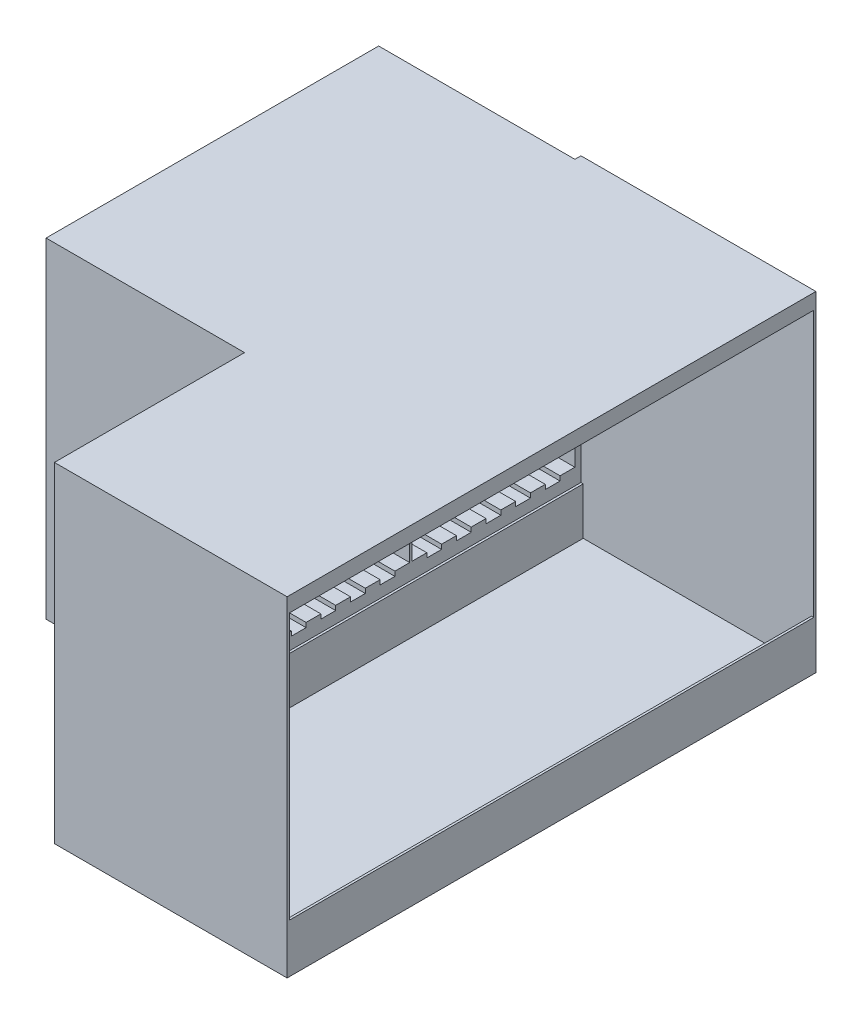
SolidWorks part; units mm, degrees
other "Исправление1"
sketch "Эскиз13" plane through (1050, -360, 1224.5) normal (0.916, -0.3443, 0.206) x (0.3981, 0.8438, -0.36)
ref_plane "Спереди" through (0, 0, 0) normal (0, 0, 1) x (1, 0, 0)
ref_plane "Сверху" through (0, 0, 0) normal (0, 1, 0) x (1, 0, 0)
ref_plane "Справа" through (0, 0, 0) normal (1, 0, 0) x (0, 0, -1)
other "Configuration Table"
sketch "Основа эскиз" plane through (0, 0, 0) normal (1, 0, 0) x (0, 0, -1)
  line L1 (-447, 435.8) -> (447, 435.8)
  line L2 (-447, 435.8) -> (-447, -435.8)
  line L3 (-447, -435.8) -> (447, -435.8)
  line L4 (447, 435.8) -> (447, -435.8)
  point P4 (0, 435.8)
  point P8 (-447, 0)
  dimension "D2" = 894
  dimension "D1" = 871.6
extrude "Основа" add sketch "Основа эскиз" along normal blind 1138.3
sketch "Вырез коретки эскиз" plane through (1138.3, 0, 0) normal (1, 0, 0) x (0, 0, -1)
  line L5 (447, 435.8) -> (-447, 435.8) construction
  line L6 (-447, 395.8) -> (441, 395.8)
  line L7 (-447, -435.8) -> (447, -435.8) construction
  line L8 (-447, 395.8) -> (-447, -305.2)
  line L9 (-447, -305.2) -> (441, -305.2)
  line L10 (441, 395.8) -> (441, -305.2)
  line L11 (-447, 435.8) -> (-447, -435.8) construction
  line L12 (447, -435.8) -> (447, 435.8) construction
  point P0 (0, 0)
  dimension "D1" = 40
  dimension "D3" = 6
  dimension "D4" = 130.6
extrude "Вырез коретки" cut sketch "Вырез коретки эскиз" against normal blind 614.3
sketch "вырез ячейки эскиз" plane through (524, 0, 0) normal (1, 0, 0) x (0, 0, -1)
  line L0 (441, 395.8) -> (-447, 395.8) construction
  line L1 (-441, 395.8) -> (-11, 395.8)
  line L2 (-441, 395.8) -> (-441, 75.8)
  line L3 (-441, 75.8) -> (-11, 75.8)
  line L4 (-11, 395.8) -> (-11, 75.8)
  line L17 (-447, 395.8) -> (-447, -305.2) construction
  dimension "D7" = 430
  dimension "D8" = 320
  dimension "D1" = 6
extrude "вырез ячейки" cut sketch "вырез ячейки эскиз" against normal blind 506
sketch "вырез двери эскиз" plane through (0, 0, 0) normal (-1, 0, 0) x (0, 0, 1)
  line L1 (11, 395.8) -> (441, 395.8)
  line L2 (11, 395.8) -> (11, 75.8)
  line L3 (11, 75.8) -> (441, 75.8)
  line L4 (441, 395.8) -> (441, 75.8)
  line L6 (441, 75.8) -> (11, 75.8) construction
  line L7 (11, 75.8) -> (11, 395.8) construction
  line L8 (441, 395.8) -> (441, 75.8) construction
  line L9 (441, 395.8) -> (441, 75.8) construction
  line L10 (11, 395.8) -> (441, 395.8) construction
extrude "вырез двери" cut sketch "вырез двери эскиз" against normal through all
sketch "Вырез основание низ эскиз" plane through (0, -305.2, 0) normal (0, 1, 0) x (1, 0, 0)
  line L0 (1138.3, -447) -> (1138.3, 441) construction
  line L1 (530, 441) -> (1132.3, 441)
  line L2 (530, 441) -> (530, -447)
  line L3 (530, -447) -> (1132.3, -447)
  line L4 (1132.3, 441) -> (1132.3, -447)
  line L5 (524, 441) -> (1138.3, 441) construction
  line L6 (524, -447) -> (1138.3, -447) construction
  dimension "D1" = 6
  dimension "D2" = 602.3
extrude "Вырез основание низ" cut sketch "Вырез основание низ эскиз" against normal blind 124.6
sketch "Вырез основания верх эскиз" plane through (0, 395.8, 0) normal (0, -1, 0) x (1, 0, 0)
  line L0 (524, 447) -> (1138.3, 447) construction
  line L1 (530, -441) -> (1132.3, -441)
  line L2 (530, -441) -> (530, 447)
  line L3 (530, 447) -> (1132.3, 447)
  line L4 (1132.3, -441) -> (1132.3, 447)
  line L5 (524, -441) -> (1138.3, -441) construction
  line L6 (1138.3, -441) -> (1138.3, 447) construction
  dimension "D1" = 6
  dimension "D2" = 602.3
extrude "Вырез основание верх" cut sketch "Вырез основания верх эскиз" against normal offset from surface (34 mm away) 6 up to face at (569.15, 435.8, 0)
sketch "вырез полозья эскиз" plane through (524, 0, 0) normal (1, 0, 0) x (0, 0, -1)
  line L0 (-441, 75.8) -> (-11, 75.8) construction
  line L1 (-401.9091, 75.8) -> (-362.8182, 75.8)
  line L2 (-401.9091, 75.8) -> (-401.9091, 63.8)
  line L3 (-401.9091, 63.8) -> (-362.8182, 63.8)
  line L4 (-362.8182, 75.8) -> (-362.8182, 63.8)
  dimension "D2" = 39.0909
  dimension "D3" = 39.0909
extrude "Вырез полозья" cut sketch "вырез полозья эскиз" against normal blind 506
pattern_linear "Линейный массив полозьев" count 5 spacing 78.1818 along (0, 0, -1) of "Вырез полозья"
pattern_linear "Линейный массив ячеек" count 2 spacing 436 along (0, 0, -1) count 2 spacing 338 along (0, -1, 0) of "Линейный массив полозьев", "вырез двери", "вырез ячейки"
sketch "Основание эскиз" plane through (0, 0, 447) normal (0, 0, 1) x (1, 0, 0)
  line L0 (1138.3, -435.8) -> (1138.3, -305.2)
  line L1 (1138.3, -305.2) -> (1132.3, -305.2)
  line L2 (1132.3, -305.2) -> (1132.3, -429.8)
  line L3 (1132.3, -429.8) -> (530, -429.8)
  line L4 (530, -429.8) -> (530, -305.2)
  line L5 (530, -305.2) -> (524, -305.2)
  line L6 (524, -305.2) -> (524, -435.8)
  line L7 (1138.3, -435.8) -> (0, -435.8) construction
  line L8 (524, -435.8) -> (1138.3, -435.8)
  line L9 (1132.3, 395.8) -> (1138.3, 395.8)
  line L10 (1138.3, 395.8) -> (1138.3, 435.8)
  line L11 (1138.3, 435.8) -> (524, 435.8)
  line L12 (1138.3, 435.8) -> (0, 435.8) construction
  line L13 (524, 435.8) -> (524, 395.8)
  line L14 (524, 395.8) -> (530, 395.8)
  line L15 (530, 395.8) -> (530, 429.8)
  line L16 (530, 429.8) -> (1132.3, 429.8)
  line L17 (1132.3, 429.8) -> (1132.3, 395.8)
extrude "Основание" add sketch "Основание эскиз" along normal blind 496
sketch "Стенка боквая эскиз" plane through (0, 0, 943) normal (0, 0, 1) x (1, 0, 0)
  line L1 (1138.3, 435.8) -> (524, 435.8)
  line L2 (1138.3, 435.8) -> (1138.3, -435.8)
  line L3 (1138.3, -435.8) -> (524, -435.8)
  line L4 (524, 435.8) -> (524, -435.8)
extrude "Стенка боковая" add sketch "Стенка боквая эскиз" along normal blind 6
sketch "Эскиз14" plane through (0, 0, -447) normal (0, 0, -1) x (-1, 0, 0)
  line L0 (-1138.3, 435.8) -> (0, 435.8) construction
  line L1 (0, -435.8) -> (-518, -435.8)
  line L2 (0, -435.8) -> (0, 435.8)
  line L3 (0, 435.8) -> (-518, 435.8)
  line L4 (-518, -435.8) -> (-518, 435.8)
  line L6 (-524, -305.2) -> (-524, 395.8) construction
  dimension "D1" = 6
extrude "Вырез-Вытянуть1" cut sketch "Эскиз14" against normal offset from surface (16 mm away) 6
sketch "Эскиз15" plane through (1138.3, 0, 0) normal (1, 0, 0) x (0, 0, -1)
  line L1 (-943, -305.2) -> (441, -305.2)
  line L2 (-943, -305.2) -> (-943, -429.8)
  line L3 (-943, -429.8) -> (441, -429.8)
  line L4 (441, -305.2) -> (441, -429.8)
extrude "Вырез-Вытянуть2" cut sketch "Эскиз15" against normal up to next
sketch "Эскиз16" plane through (1138.3, 0, 0) normal (1, 0, 0) x (0, 0, -1)
  line L0 (441, -306.58) -> (441, -429.8)
  line L2 (-943, -429.8) -> (441, -429.8)
  line L3 (-943, -429.8) -> (-943, -306.58)
  line L4 (-943, -306.58) -> (441, -306.58)
  line L7 (441, -429.8) -> (441, 395.8) construction
  dimension "D1" = 123.22
extrude "Бобышка-Вытянуть1" add sketch "Эскиз16" against normal blind 6
equation "\"Ширина груза\"= 420"
equation "\"Глубина груза\"= 490"
equation "\"Высота груза\"= 297"
equation "\"Ширина ячейки\"= \"Ширина груза\" + 10"
equation "\"Глубина ячейки\"= \"Глубина груза\" + 10"
equation "\"Высота ячейки\"= \"Высота груза\" + 10 + 13"
equation "\"Колво ячеек ширина\"= 2"
equation "\"Колво ячеек высота\"= 2"
equation "\"Толщина стенки\" = 6"
equation "\"D2@Основа эскиз\"=( \"Ширина ячейки\" + \"Толщина стенки\" + \"Крепление дверцы\" ) * \"Колво ячеек ширина\" + \"Толщина стенки\"*2"
equation "\"D1@Основа эскиз\"=( \"Высота ячейки\" + \"Толщина стенки\" + \"Высота пола\" ) * \"Колво ячеек высота\" + \"Толщина стенки\" * 6 + \"Мотор X ширина корпуса\" + \"Мотор Y ширина корпуса\"+40+20+15"
equation "\"Крепление дверцы\"= 5 "
equation "\"D7@вырез ячейки эскиз\"= \"Ширина ячейки\""
equation "\"D1@вырез ячейки эскиз\"=\"Толщина стенки\" "
equation "\"D8@вырез ячейки эскиз\"= \"Высота ячейки\""
equation "\"D1@Основа\"=\"Глубина ячейки\" + \"Глубина каретки\" + \"Толщина стенки\" * 6 + \"Ширина рейки\""
equation "\"D1@Вырез коретки\"=\"Глубина каретки\" + \"Толщина стенки\" * 2 + \"Ширина рейки\""
equation "\"D1@Вырез основание низ эскиз\"=\"Толщина стенки\" "
equation "\"Ширина рейки\"= \"Толщина шестерни\""
equation "\"D1@вырез ячейки\"= \"Глубина ячейки\" + \"Толщина стенки\""
equation "\"D1\"= \"Толщина стенки\""
equation "\"D2@Вырез основание низ эскиз\"=\"Глубина каретки\" + \"Ширина рейки\""
equation "\"Высота рейки\"= 20"
equation "\"D1@Вырез основания верх эскиз\"=\"Толщина стенки\""
equation "\"D2@Вырез основания верх эскиз\"=\"Глубина каретки\" + \"Ширина рейки\" "
equation "\"D1@Вырез основание верх\"=\"Толщина стенки\""
equation "\"D4@Вырез коретки эскиз\"=\"Толщина стенки\"  + \"Высота рейки\" + \"Отступ рейки\" + \"Мотор X ширина корпуса\" + \"Мотор Y ширина корпуса\""
equation "\"D1@Вырез коретки эскиз\"=\"Толщина стенки\"*2+28"
equation "\"D3@Вырез коретки эскиз\" = \"Толщина стенки\""
equation "\"D1@Вырез основание низ\"=\"Мотор X ширина корпуса\" + \"Мотор Y ширина корпуса\"+\"Высота рейки\" + \"Отступ рейки\""
equation "\"Высота пола\"= \"Толщина стенки\" * 2"
equation "\"Колво полозьев\"= 5"
equation "\"D1@вырез полозья эскиз\" = \"Высота пола\""
equation "\"D2@вырез полозья эскиз\" = \"Ширина ячейки\" /  ( \"Колво полозьев\" * 2 + 1 ) "
equation "\"D3@вырез полозья эскиз\"= \"Ширина ячейки\" / ( \"Колво полозьев\" * 2 + 1 )"
equation "\"D1@Вырез полозья\" = \"Глубина ячейки\" + \"Толщина стенки\""
equation "\"D1@Линейный массив полозьев\" = \"Колво полозьев\""
equation "\"D3@Линейный массив полозьев\" = \"Ширина ячейки\" /  ( \"Колво полозьев\" * 2 + 1 )  * 2"
equation "\"D1@Линейный массив ячеек\" = \"Колво ячеек ширина\""
equation "\"D2@Линейный массив ячеек\" = \"Колво ячеек высота\""
equation "\"D3@Линейный массив ячеек\" = \"Ширина ячейки\" + \"Толщина стенки\""
equation "\"D4@Линейный массив ячеек\" = \"Высота ячейки\" + \"Высота пола\" + \"Толщина стенки\""
equation "\"Отступ рейки\"= 20"
equation "\"Глубина каретки\"= \"Глубина ячейки\" + 30 + \"Мотор Y высота корпуса\" + 20"
equation "\"D1@Стенка боковая\" = \"Толщина стенки\""
equation "\"Длинна рейки\"= ( \"Ширина ячейки\" + \"Толщина стенки\" + \"Крепление дверцы\" ) * \"Колво ячеек ширина\" + \"Ширина ячейки выгрузки\" * \"Колво выгрузки\" + \"Толщина стенки\""
equation "\"D1@Основание\" = \"Длинна рейки\" -  ( \"Ширина ячейки\" + \"Толщина стенки\" + \"Крепление дверцы\" )  * \"Колво ячеек ширина\" - \"Толщина стенки\""
equation "\"Отступ шпильки\"= 26"
equation "\"Диаметр шпильки\"= 5"
equation "\"Длинна шпильки\"= ( \"Высота ячейки\" + \"Толщина стенки\" + \"Высота пола\" ) * \"Колво ячеек высота\" + ( \"Толщина стенки\" + \"Отступ рейки\" ) * 2 "
equation "\"Ширина пластины\"= 50  "
equation "\"Высота зона выгрузки\"= \"Высота ячейки\" * 2 + \"Толщина стенки\" * 2"
equation "\"Колво выгрузки\"= 1"
equation "\"D1@Вырез-Вытянуть1\"=\"Толщина стенки\""
equation "\"Ширина ячейки выгрузки\"= \"Ширина ячейки\" + \"Толщина стенки\" + \"Отступ крепления мотора фиксации\"*2"
equation "\"Отступ крепления мотора фиксации\" = 30"
equation "\"Мотор X ширина корпуса\"= 42.3"
equation "\"Мотор X высота корпуса\"= 42.3"
equation "\"Мотор X длина корпуса\"= 40"
equation "\"Мотор X вылет вала\"= 19.8"
equation "\"Мотор Y ширина корпуса\"= 42.3"
equation "\"Мотор Y высота корпуса\"= 42.3"
equation "\"Мотор Y длина корпуса\"= 48"
equation "\"Мотор Y вылет вала\"= 30"
equation "\"Мотор Z ширина корпуса\"= 42"
equation "\"Мотор Z высота корпуса\"= 42"
equation "\"Мотор Z длина корпуса\"= 40"
equation "\"Мотор Z вылет вала\"= 23"
equation "\"Мотор диаметр вала ПРЕДВ\"= 5"
equation "\"Мотор шаг крепления ПРЕДВ\"= 31"
equation "\"Мотор диаметр отверстий ПРЕДВ\"= 3"
equation "\"Мотор глубина отверстий ПРЕДВ\"= 4.5"
equation "\"Мотор диаметр буртика ПРЕДВ\"= 22"
equation "\"Мотор высота буртика ПРЕДВ\"= 2"
equation "\"Мотор диаметр шкива ПРЕДВ\"= 16"
equation "\"Мотор длина шкива ПРЕДВ\"= 12"
equation "\"Мотор отступ шкива ПРЕДВ\"= 5"
equation "\"Мотор X шаг градусов\"= 1.8"
equation "\"Мотор Y шаг градусов\"= 1.8"
equation "\"Мотор Z шаг градусов\"= 1.8"
equation "\"Мотор Y диаметр ротора\"= 25.78"
equation "\"Толщина шестерни\"= 10"
equation "\"D1@Бобышка-Вытянуть1\"=\"Толщина стенки\""
equation "\"D1@Эскиз14\"=\"Толщина стенки\""
